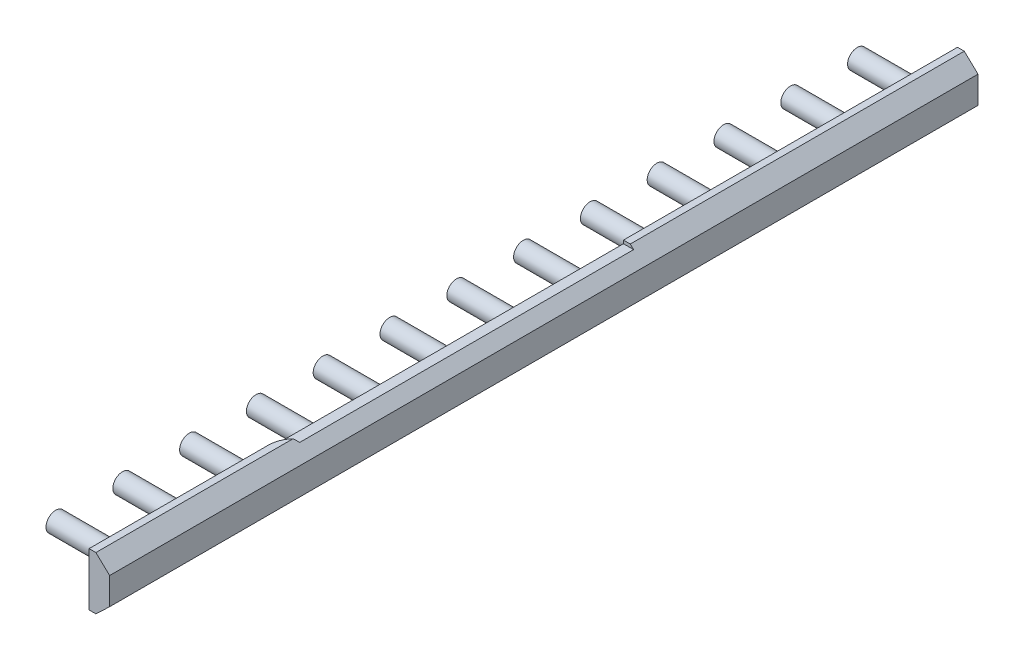
SolidWorks part; units mm, degrees
ref_plane "Front Plane" through (0, 0, 0) normal (0, 0, 1) x (1, 0, 0)
ref_plane "Top Plane" through (0, 0, 0) normal (0, 1, 0) x (1, 0, 0)
ref_plane "Right Plane" through (0, 0, 0) normal (1, 0, 0) x (0, 0, -1)
sketch "Sketch1" plane through (0, 0, 0) normal (0, 0, 1) x (1, 0, 0)
  line B0 (0, 7.95) -> (2.04, 7.95)
  line B1 (6.1524, 4.048) -> (6.1524, -4.048)
  line B2 (2.04, -7.95) -> (0, -7.95)
  line B3 (0, -7.95) -> (0, 7.95)
  line B4 (2.04, 7.95) -> (6.1524, 4.048)
  line B5 (6.1524, -4.048) -> (2.04, -7.95)
sketch_block_instance "Extrusion Profile-1"
sketch_block "Extrusion Profile" parameters "D1"=8.44, "D2"=2.6, "D3"=6, "D4"=16.7, "D6"=5.6686, "D7"=2.0404, "D8"=8.0963, "D9"=15.9, "D5"=2.4157
extrude "Boss-Extrude1" add sketch "Sketch1" along normal blind 260
sketch "Sketch2" plane through (0, 0, 0) normal (-1, 0, 0) x (0, 0, 1)
  circle A0 centre (10, 0) radius 2.9
  circle A1 centre (30, 0) radius 2.9
  circle A2 centre (50, 0) radius 2.9
  circle A3 centre (70, 0) radius 2.9
  circle A4 centre (90, 0) radius 2.9
  circle A5 centre (110, 0) radius 2.9
  circle A6 centre (130, 0) radius 2.9
  circle A7 centre (150, 0) radius 2.9
  circle A8 centre (170, 0) radius 2.9
  circle A9 centre (190, 0) radius 2.9
  circle A10 centre (210, 0) radius 2.9
  circle A11 centre (230, 0) radius 2.9
  circle A12 centre (250, 0) radius 2.9
  dimension "D2" = 5.8
  dimension "D1" = 10
  dimension "D4" = 20
  dimension "D3" = 13
extrude "Boss-Extrude2" add sketch "Sketch2" along normal blind 20
sketch "Sketch3" plane through (0, 0, 0) normal (-1, 0, 0) x (0, 0, 1)
  line L0 (190, 0) -> (210, 0) construction
  line L1 (200, 0) -> (200, 7.95) construction
  line L2 (260, 7.95) -> (0, 7.95) construction
  line L3 (200, 7.95) -> (200, 7)
  line L4 (200, 7) -> (100, 7)
  line L5 (100, 7) -> (100, 7.95)
  line L6 (100, 7.95) -> (200, 7.95)
  line L7 (90, 0) -> (110, 0) construction
  line L8 (100, 0) -> (100, 7) construction
  point P17 (100.4724, 4)
  dimension "D1" = 7
extrude "Cut-Extrude1" cut sketch "Sketch3" against normal through all
chamfer "Chamfer1" distance 3 angle 45 1 edges at (0, 7.475, 200)
fillet "Fillet1" radius 8 1 edges at (0, 7.475, 203)
